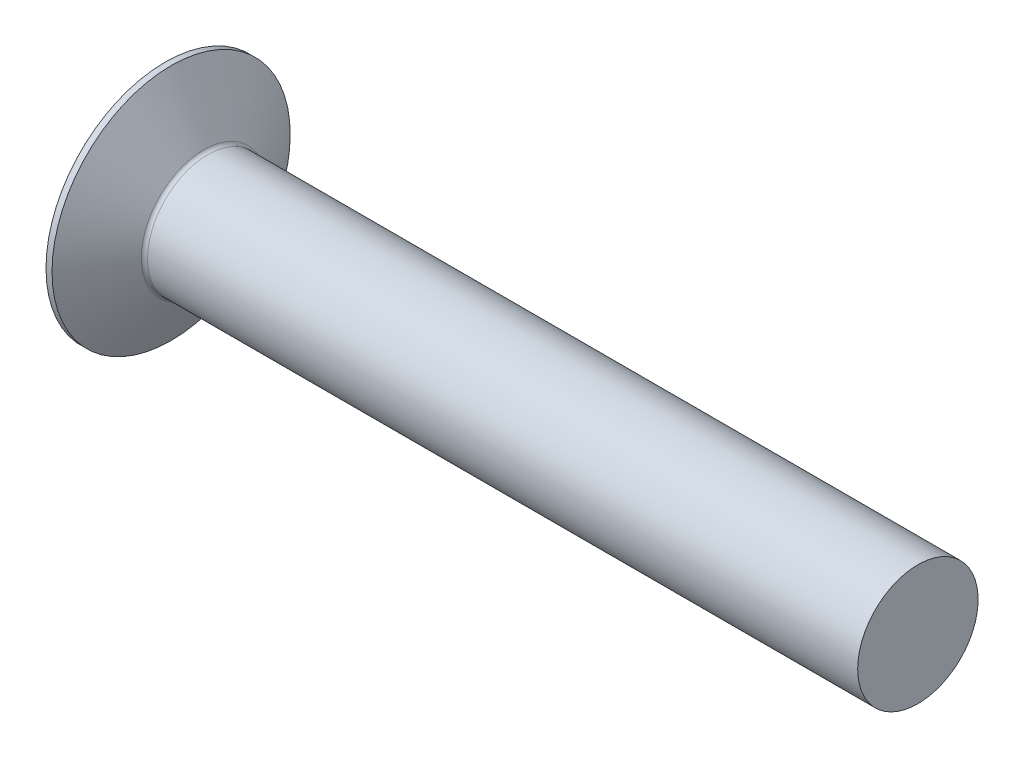
SolidWorks part; units mm, degrees
ref_plane "Front" through (0, 0, 0) normal (0, 0, 1) x (1, 0, 0)
ref_plane "Top" through (0, 0, 0) normal (0, 1, 0) x (1, 0, 0)
ref_plane "Right" through (0, 0, 0) normal (1, 0, 0) x (0, 0, -1)
sketch "Sketch1" plane through (0, 0, 0) normal (0, 0, 1) x (1, 0, 0)
  line L0 (-69.0696, 0) -> (10.536, 0) construction
  line L1 (50, 0) -> (50, 4)
  line L2 (50, 4) -> (2.8306, 4)
  line L3 (2.5708, 4.15) -> (0.4, 7.91)
  line L4 (0.4, 7.91) -> (0, 7.91)
  line L5 (0, 7.91) -> (0, 0)
  line L6 (50, 0) -> (0, 0)
  arc A0 (2.8306, 4) -> (2.5708, 4.15) centre (2.8306, 4.3) cw
  dimension "r" = 0.3
  dimension "d" = 8
  dimension "l" = 50
  dimension "D3" = 60
  dimension "dk" = 15.82
  dimension "K" = 0.4
revolve "Base-Revolve" add sketch "Sketch1" angle 360 about L0
